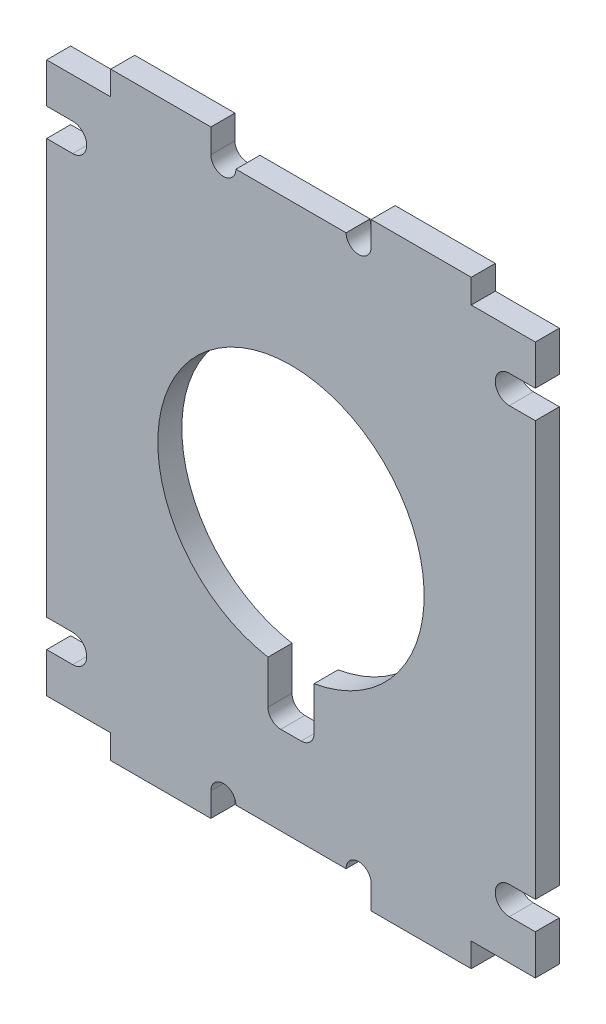
SolidWorks part; units mm, degrees
material "Thornel Mat VMA"
ref_plane "Front Plane" through (0, 0, 0) normal (0, 0, 1) x (1, 0, 0)
ref_plane "Top Plane" through (0, 0, 0) normal (0, 1, 0) x (1, 0, 0)
ref_plane "Right Plane" through (0, 0, 0) normal (1, 0, 0) x (0, 0, -1)
sketch "Sketch1" plane through (0, 0, 0) normal (0, 0, 1) x (1, 0, 0)
  line L0 (15.494, 17.4625) -> (-15.494, -17.4625) construction
  line L1 (-15.494, 17.4625) -> (15.494, 17.4625)
  line L2 (-15.494, 17.4625) -> (-15.494, -17.4625)
  line L3 (-15.494, -17.4625) -> (15.494, -17.4625)
  line L4 (15.494, 17.4625) -> (15.494, -17.4625)
  line L5 (-15.494, 17.4625) -> (15.494, -17.4625) construction
  dimension "D1" = 34.925
  dimension "D2" = 30.988
extrude "Boss-Extrude1" add sketch "Sketch1" along normal blind 1.524
sketch "Sketch2" plane through (0, 0, 1.524) normal (0, 0, 1) x (1, 0, 0)
  line L0 (15.494, 17.4625) -> (-15.494, -17.4625) construction
  line L1 (-15.494, 17.4625) -> (15.494, -17.4625) construction
  line L2 (-1.4605, -8.3183) -> (-1.4605, -11.0617)
  line L3 (-0.6477, -11.8745) -> (0.6477, -11.8745)
  line L4 (1.4605, -8.3183) -> (1.4605, -11.0617)
  circle A0 centre (0, 0) radius 8.4455
  arc A1 (1.4605, -11.0617) -> (0.6477, -11.8745) centre (0.6477, -11.0617) cw
  arc A2 (-0.6477, -11.8745) -> (-1.4605, -11.0617) centre (-0.6477, -11.0617) cw
  point P7 (0, -11.8745)
  point P18 (1.4605, -11.8745)
  point P21 (-1.4605, -11.8745)
  dimension "D1" = 16.891
  dimension "D4" = 0.8128
  dimension "D2" = 2.921
  dimension "D3" = 20.32
extrude "Cut-Extrude1" cut sketch "Sketch2" against normal through all contours A0 | A2 L3 A1 L4 A0 L2 region at (0, -10.0939, 1.524) region at (0, 0, 1.524)
sketch "Sketch3" plane through (0, 0, 1.524) normal (0, 0, 1) x (1, 0, 0)
  line L0 (15.494, -17.4625) -> (15.494, 17.4625) construction
  line L1 (15.494, 17.4625) -> (-15.494, 17.4625) construction
  line L6 (15.494, 14.0335) -> (13.843, 14.0335) construction
  line L7 (15.494, 13.1445) -> (13.843, 13.1445)
  line L8 (15.494, 14.9225) -> (13.843, 14.9225)
  arc A0 (15.494, 13.1445) -> (15.494, 14.9225) centre (15.494, 14.0335) ccw
  arc A1 (13.843, 14.9225) -> (13.843, 13.1445) centre (13.843, 14.0335) ccw
  point P10 (14.6685, 14.0335)
  dimension "D1" = 2.54
  dimension "D4" = 1.778
  dimension "D5" = 2.54
extrude "Cut-Extrude2" cut sketch "Sketch3" against normal through all
sketch "Sketch4" plane through (0, 0, 1.524) normal (0, 0, 1) x (1, 0, 0)
  line L0 (15.494, 17.4625) -> (-15.494, 17.4625) construction
  line L1 (5.08, 18.9865) -> (11.43, 18.9865)
  line L2 (5.08, 18.9865) -> (5.08, 17.4625)
  line L3 (5.08, 17.4625) -> (11.43, 17.4625)
  line L4 (11.43, 18.9865) -> (11.43, 17.4625)
  line L5 (0, 0) -> (0, 26.7589) construction
  circle A0 centre (4.2862, 17.4625) radius 0.7937
  line M17 (15.494, 17.4625) -> (-15.494, 17.4625)
  dimension "D4" = 1.5875
  dimension "D1" = 1.524
  dimension "D2" = 10.16
  dimension "D3" = 6.35
extrude "Boss-Extrude2" add sketch "Sketch4" against normal up to surface (1.524 mm away) contours L4 L1 L2 M17 region at (8.255, 18.2245, 1.524) up to face at (0, -7.6803, 0)
extrude "Cut-Extrude3" cut sketch "Sketch4<3>" against normal through all contours A0
sketch "Sketch4<3>" plane through (0, 0, 1.524) normal (0, 0, 1) x (1, 0, 0) same geometry as "Sketch4"
mirror "Mirror3" about plane through (0, 0, 0) normal (0, 1, 0) of "Cut-Extrude2", "Boss-Extrude2", "Cut-Extrude3"
mirror "Mirror4" about plane through (0, 0, 0) normal (1, 0, 0) of "Cut-Extrude3", "Boss-Extrude2", "Mirror3"
ref_axis "CAMERA AXIS" through (0, 0, 0) along (0, 0, 1)
